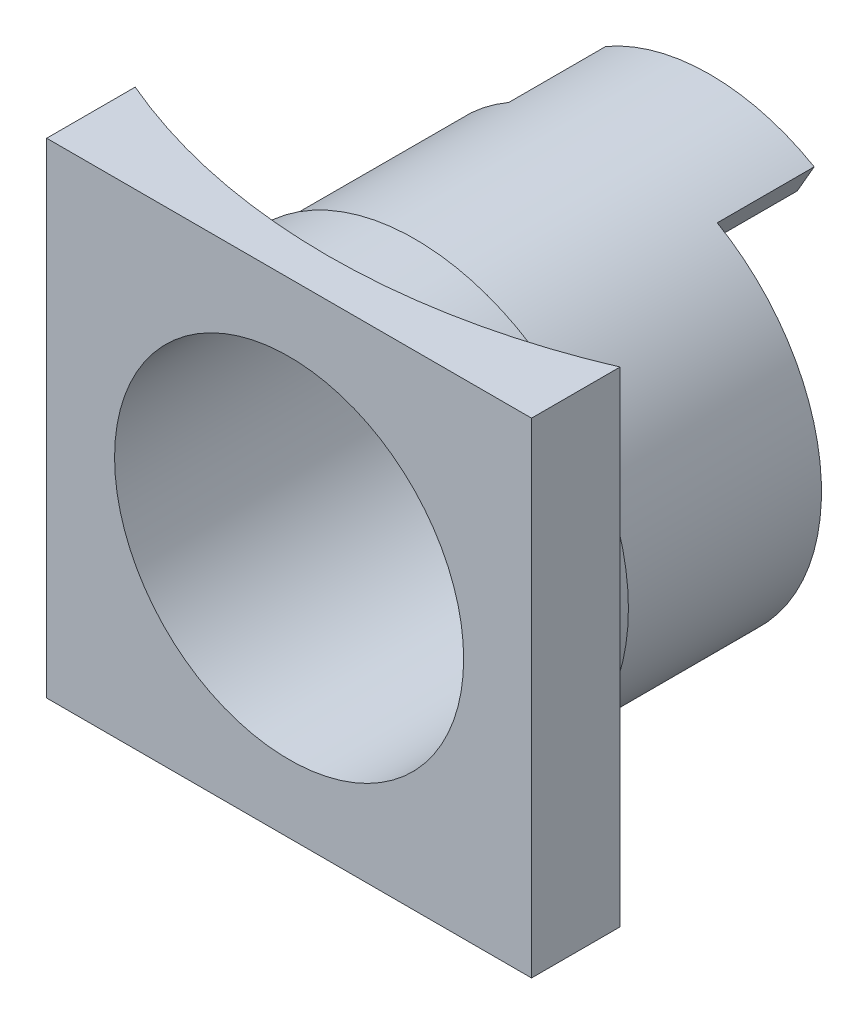
SolidWorks part; units mm, degrees
ref_plane "Спереди" through (0, 0, 0) normal (0, 0, 1) x (1, 0, 0)
ref_plane "Сверху" through (0, 0, 0) normal (0, 1, 0) x (1, 0, 0)
ref_plane "Справа" through (0, 0, 0) normal (1, 0, 0) x (0, 0, -1)
sketch "Эскиз1" plane through (0, 0, 0) normal (0, 1, 0) x (1, 0, 0)
  line L0 (0, 31.75) -> (0, -31.75) construction
  line L1 (-12.5, -29.1858) -> (12.5, -29.1858) construction
  line L2 (-12.5, -29.1858) -> (-12.5, -33.75)
  line L3 (-12.5, -33.75) -> (12.5, -33.75)
  line L4 (12.5, -33.75) -> (12.5, -29.1858)
  circle A0 centre (0, 0) radius 31.75 construction
  arc A1 (-12.5, -29.1858) -> (12.5, -29.1858) centre (0, 0) ccw
  dimension "D1" = 63.5
  dimension "D2" = 25
  dimension "D3" = 2
extrude "Вытянуть1" add sketch "Эскиз1" along normal blind 25
sketch "Эскиз2" plane through (0, 0, 33.75) normal (0, 0, 1) x (1, 0, 0)
  line L0 (12.5, 25) -> (12.5, 0) construction
  circle A0 centre (0, 12.5) radius 9
  dimension "D1" = 18
  dimension "D2" = 12.5
  dimension "D3" = 12.5
extrude "Вытянуть2" cut sketch "Эскиз2" against normal through all
sketch "Эскиз3" plane through (0, 0, 33.75) normal (0, 0, 1) x (1, 0, 0)
  circle A0 centre (0, 12.5) radius 9
  circle A1 centre (0, 12.5) radius 9 construction
  circle A2 centre (0, 12.5) radius 11
  dimension "D1" = 22
extrude "tube" add sketch "Эскиз3" against normal blind 16.7
sketch "Эскиз4" plane through (0, 0, 17.05) normal (0, 0, -1) x (-1, 0, 0)
  line L0 (-4.5, 20.2942) -> (-5.5, 22.0263)
  line L1 (4.5, 20.2942) -> (5.5, 22.0263)
  line L2 (0, 12.5) -> (0, 23.5) construction
  line L3 (0, 12.5) -> (-5.5, 22.0263) construction
  line L4 (0, 12.5) -> (5.5, 22.0263) construction
  circle A0 centre (0, 12.5) radius 9 construction
  circle A1 centre (0, 12.5) radius 11 construction
  circle A2 centre (0, 12.5) radius 11 construction
  arc A3 (-4.5, 20.2942) -> (4.5, 20.2942) centre (0, 12.5) cw
  arc A4 (-5.5, 22.0263) -> (5.5, 22.0263) centre (0, 12.5) cw
  dimension "D1" = 30
  dimension "D2" = 30
extrude "support" add sketch "Эскиз4" along normal blind 5
sketch "Эскиз5" plane through (0, 0, 12.05) normal (0, 0, -1) x (-1, 0, 0)
  circle A0 centre (0, 12.5) radius 11
  circle A1 centre (0, 12.5) radius 10.75
  circle A2 centre (0, 12.5) radius 11 construction
  dimension "D1" = 21.5
extrude "holder" cut sketch "Эскиз5" against normal blind 15.205
